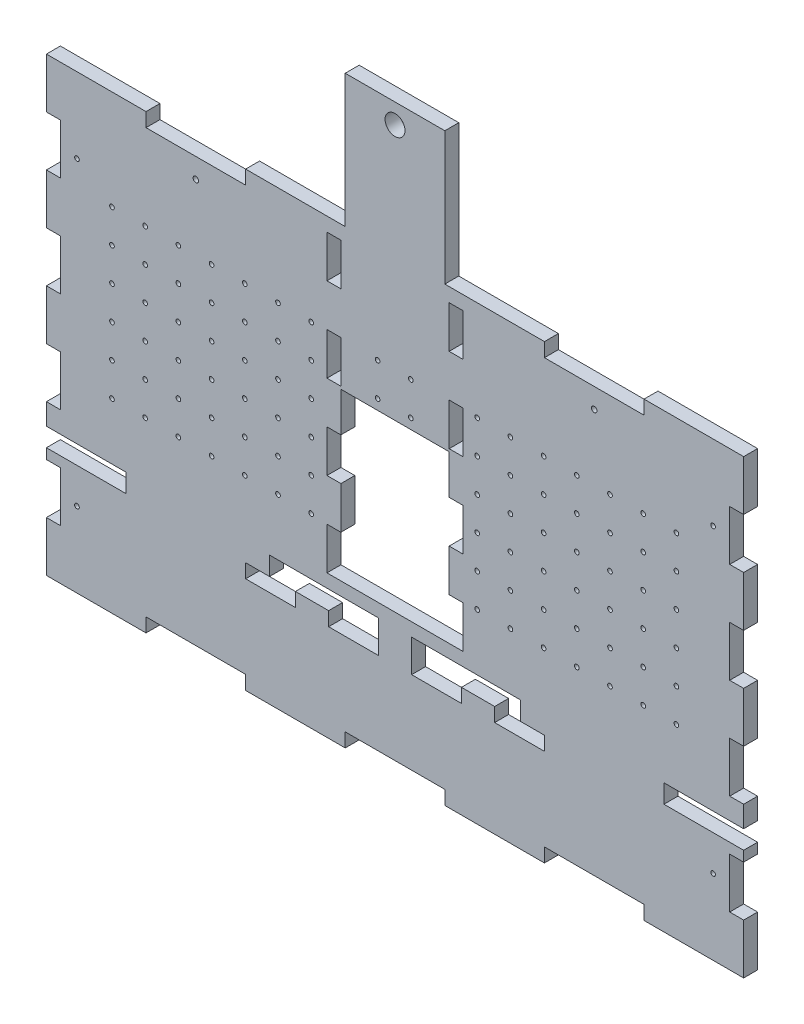
SolidWorks part; units mm, degrees
ref_plane "Front Plane" through (0, 0, 0) normal (0, 0, 1) x (1, 0, 0)
ref_plane "Top Plane" through (0, 0, 0) normal (0, 1, 0) x (1, 0, 0)
ref_plane "Right Plane" through (0, 0, 0) normal (1, 0, 0) x (0, 0, -1)
sketch "Sketch1" plane through (0, 0, 0) normal (0, 0, 1) x (1, 0, 0)
  line L1 (-127.8759, 88.4641) -> (138.8241, 88.4641)
  line L2 (-127.8759, 88.4641) -> (-127.8759, -84.2559)
  line L3 (-127.8759, -84.2559) -> (138.8241, -84.2559)
  line L4 (138.8241, 88.4641) -> (138.8241, -84.2559)
  dimension "D1" = 266.7
  dimension "D2" = 172.72
extrude "Boss-Extrude1" add sketch "Sketch1" along normal blind 5.334
sketch "Sketch2" plane through (0, 0, 5.334) normal (0, 0, 1) x (1, 0, 0)
  line L0 (-127.8759, -84.2559) -> (138.8241, -84.2559) construction
  line L1 (-89.7759, -84.2559) -> (-51.6759, -84.2559)
  line L2 (-89.7759, -84.2559) -> (-89.7759, -78.9219)
  line L3 (-89.7759, -78.9219) -> (-51.6759, -78.9219)
  line L4 (-51.6759, -84.2559) -> (-51.6759, -78.9219)
  line L5 (-89.7759, -78.9219) -> (-127.8759, -78.9219) construction
  line L6 (-13.5759, -84.2559) -> (24.5241, -84.2559)
  line L7 (-13.5759, -84.2559) -> (-13.5759, -78.9219)
  line L8 (-13.5759, -78.9219) -> (24.5241, -78.9219)
  line L9 (24.5241, -84.2559) -> (24.5241, -78.9219)
  line L10 (62.6241, -84.2559) -> (100.7241, -84.2559)
  line L11 (62.6241, -84.2559) -> (62.6241, -78.9219)
  line L12 (62.6241, -78.9219) -> (100.7241, -78.9219)
  line L13 (100.7241, -84.2559) -> (100.7241, -78.9219)
  line L14 (-127.8759, 88.4641) -> (-127.8759, -84.2559) construction
  line L15 (-51.6759, -78.9219) -> (-13.5759, -78.9219) construction
  line L16 (24.5241, -78.9219) -> (62.6241, -78.9219) construction
  line L17 (62.6241, -78.9219) -> (62.364, -79.7896) construction
  line L18 (100.7241, -78.9219) -> (138.8241, -78.9219) construction
  line L19 (138.8241, -84.2559) -> (138.8241, 88.4641) construction
  line L20 (-127.8759, 2.1041) -> (138.8241, 2.1041) construction
  line L21 (100.7241, 88.4641) -> (100.7241, 83.1301)
  line L22 (62.6241, 83.1301) -> (100.7241, 83.1301)
  line L23 (62.6241, 88.4641) -> (62.6241, 83.1301)
  line L24 (24.5241, 88.4641) -> (24.5241, 83.1301)
  line L25 (-13.5759, 83.1301) -> (24.5241, 83.1301)
  line L26 (-13.5759, 88.4641) -> (-13.5759, 83.1301)
  line L27 (-51.6759, 88.4641) -> (-51.6759, 83.1301)
  line L28 (-89.7759, 83.1301) -> (-51.6759, 83.1301)
  line L29 (-89.7759, 88.4641) -> (-89.7759, 83.1301)
  line L30 (62.6241, 88.4641) -> (100.7241, 88.4641)
  line L31 (-13.5759, 88.4641) -> (24.5241, 88.4641)
  line L32 (-89.7759, 88.4641) -> (-51.6759, 88.4641)
  dimension "D1" = 5.334
extrude "Cut-Extrude1" cut sketch "Sketch2" against normal through all
sketch "Sketch5" plane through (0, 0, 5.334) normal (0, 0, 1) x (1, 0, 0)
  line L0 (5.4741, 83.1301) -> (5.4741, -78.9219) construction
  line L1 (-13.5759, 83.1301) -> (24.5241, 83.1301) construction
  line L2 (24.5241, -78.9219) -> (-13.5759, -78.9219) construction
  line L3 (11.8241, -34.8224) -> (11.8241, -41.9344)
  line L4 (-42.5319, -34.8224) -> (-0.8759, -34.8224)
  line L5 (-42.5319, -34.8224) -> (-42.5319, -41.9344)
  line L6 (-42.5319, -41.9344) -> (-0.8759, -41.9344)
  line L7 (-0.8759, -34.8224) -> (-0.8759, -41.9344)
  line L8 (53.4801, -41.9344) -> (11.8241, -41.9344)
  line L9 (53.4801, -34.8224) -> (53.4801, -41.9344)
  line L10 (53.4801, -34.8224) -> (11.8241, -34.8224)
  line L11 (11.8241, -34.8224) -> (-0.8759, -34.8224) construction
  line L12 (-0.8759, -41.9344) -> (11.8241, -41.9344) construction
  line L13 (-139.0519, -34.8224) -> (-97.3959, -34.8224)
  line L14 (-139.0519, -34.8224) -> (-139.0519, -41.9344)
  line L15 (-139.0519, -41.9344) -> (-97.3959, -41.9344)
  line L16 (-97.3959, -34.8224) -> (-97.3959, -41.9344)
  line L18 (108.3441, -34.8224) -> (108.3441, -41.9344)
  line L19 (150.0001, -41.9344) -> (108.3441, -41.9344)
  line L20 (150.0001, -34.8224) -> (150.0001, -41.9344)
  line L21 (150.0001, -34.8224) -> (108.3441, -34.8224)
  dimension "D2" = 41.656
  dimension "D3" = 6.35
  dimension "D1" = 7.112
  dimension "D4" = 2
extrude "Cut-Extrude3" cut sketch "Sketch5" against normal through all
sketch "Sketch9" plane through (0, 0, 5.334) normal (0, 0, 1) x (1, 0, 0)
  line L0 (-127.8759, 88.4641) -> (-127.8759, -34.8224) construction
  line L1 (-127.8759, -65.0647) -> (-122.5419, -65.0647)
  line L2 (-127.8759, -65.0647) -> (-127.8759, -45.8736)
  line L3 (-127.8759, -45.8736) -> (-122.5419, -45.8736)
  line L4 (-122.5419, -65.0647) -> (-122.5419, -45.8736)
  line L5 (-122.5419, 69.273) -> (-122.5419, 88.4641) construction
  line L6 (-127.8759, -26.6825) -> (-122.5419, -26.6825)
  line L7 (-127.8759, -26.6825) -> (-127.8759, -7.4914)
  line L8 (-127.8759, -7.4914) -> (-122.5419, -7.4914)
  line L9 (-122.5419, -26.6825) -> (-122.5419, -7.4914)
  line L10 (-127.8759, 11.6997) -> (-122.5419, 11.6997)
  line L11 (-127.8759, 11.6997) -> (-127.8759, 30.8908)
  line L12 (-127.8759, 30.8908) -> (-122.5419, 30.8908)
  line L13 (-122.5419, 11.6997) -> (-122.5419, 30.8908)
  line L14 (-127.8759, 50.0819) -> (-122.5419, 50.0819)
  line L15 (-127.8759, 50.0819) -> (-127.8759, 69.273)
  line L16 (-127.8759, 69.273) -> (-122.5419, 69.273)
  line L17 (-122.5419, 50.0819) -> (-122.5419, 69.273)
  line L18 (-89.7759, 88.4641) -> (-127.8759, 88.4641) construction
  line L19 (-122.5419, 50.0819) -> (-122.5419, 30.8908) construction
  line L20 (-122.5419, 11.6997) -> (-122.5419, -7.4914) construction
  line L21 (-122.5419, -26.6825) -> (-122.5419, -45.8736) construction
  line L22 (-122.5419, -65.0647) -> (-122.5419, -84.2559) construction
  line L23 (-127.8759, -84.2559) -> (-89.7759, -84.2559) construction
  line L24 (5.4741, 83.1301) -> (5.4741, -78.9219) construction
  line L25 (-13.5759, 83.1301) -> (24.5241, 83.1301) construction
  line L26 (24.5241, -78.9219) -> (-13.5759, -78.9219) construction
  line L27 (133.4901, -65.0647) -> (133.4901, -84.2559) construction
  line L28 (133.4901, -26.6825) -> (133.4901, -45.8736) construction
  line L29 (133.4901, 11.6997) -> (133.4901, -7.4914) construction
  line L30 (133.4901, 50.0819) -> (133.4901, 30.8908) construction
  line L31 (133.4901, 69.273) -> (133.4901, 88.4641) construction
  line L32 (133.4901, 50.0819) -> (133.4901, 69.273)
  line L33 (138.8241, 69.273) -> (133.4901, 69.273)
  line L34 (138.8241, 50.0819) -> (138.8241, 69.273)
  line L35 (138.8241, 50.0819) -> (133.4901, 50.0819)
  line L36 (133.4901, 11.6997) -> (133.4901, 30.8908)
  line L37 (138.8241, 30.8908) -> (133.4901, 30.8908)
  line L38 (138.8241, 11.6997) -> (138.8241, 30.8908)
  line L39 (138.8241, 11.6997) -> (133.4901, 11.6997)
  line L40 (133.4901, -26.6825) -> (133.4901, -7.4914)
  line L41 (138.8241, -7.4914) -> (133.4901, -7.4914)
  line L42 (138.8241, -26.6825) -> (138.8241, -7.4914)
  line L43 (138.8241, -26.6825) -> (133.4901, -26.6825)
  line L44 (133.4901, -65.0647) -> (133.4901, -45.8736)
  line L45 (138.8241, -45.8736) -> (133.4901, -45.8736)
  line L46 (138.8241, -65.0647) -> (138.8241, -45.8736)
  line L47 (138.8241, -65.0647) -> (133.4901, -65.0647)
  dimension "D1" = 5.334
extrude "Cut-Extrude7" cut sketch "Sketch9" against normal through all
sketch "Sketch10" plane through (0, 88.4641, 0) normal (0, 1, 0) x (1, 0, 0)
  line L1 (24.5241, -5.334) -> (62.6241, -5.334)
  line L2 (24.5241, -5.334) -> (24.5241, 0)
  line L3 (24.5241, 0) -> (62.6241, 0)
  line L4 (62.6241, -5.334) -> (62.6241, 0)
extrude "Boss-Extrude2" add sketch "Sketch10" along normal blind 50.8
sketch "Sketch11" plane through (0, 0, 0) normal (0, 0, -1) x (-1, 0, 0)
  line L0 (-24.5241, 83.1301) -> (-24.5241, 139.2641) construction
  line L1 (-24.5241, 88.4641) -> (-31.1281, 88.4641)
  line L2 (-24.5241, 88.4641) -> (-24.5241, 129.1041)
  line L3 (-24.5241, 129.1041) -> (-31.1281, 129.1041)
  line L4 (-31.1281, 88.4641) -> (-31.1281, 129.1041)
  line L5 (13.5759, 88.4641) -> (51.6759, 88.4641) construction
  dimension "D1" = 6.604
  dimension "D3" = 0
extrude "Cut-Extrude8" cut sketch "Sketch11" against normal through all
sketch "Sketch12" plane through (0, 0, 5.334) normal (0, 0, 1) x (1, 0, 0)
  line L0 (62.6241, 139.2641) -> (62.6241, 83.1301) construction
  circle A0 centre (43.5741, 130.4765) radius 3.81
  dimension "D1" = 19.05
extrude "Cut-Extrude9" cut sketch "Sketch12" against normal through all
sketch "Sketch14" plane through (0, 0, 5.334) normal (0, 0, 1) x (1, 0, 0)
  line L0 (-89.7759, 88.4641) -> (-127.8759, 88.4641) construction
  circle A0 centre (-102.7976, 50.3641) radius 0.889
  circle A1 centre (-90.0976, 50.3641) radius 0.889
  circle A2 centre (-77.3976, 50.3641) radius 0.889
  circle A3 centre (-64.6976, 50.3641) radius 0.889
  circle A4 centre (-51.9976, 50.3641) radius 0.889
  circle A5 centre (-39.2976, 50.3641) radius 0.889
  circle A6 centre (-26.5976, 50.3641) radius 0.889
  circle A8 centre (-1.1976, 50.3641) radius 0.889
  circle A9 centre (11.5024, 50.3641) radius 0.889
  circle A11 centre (36.9024, 50.3641) radius 0.889
  circle A12 centre (49.6024, 50.3641) radius 0.889
  circle A13 centre (62.3024, 50.3641) radius 0.889
  circle A14 centre (75.0024, 50.3641) radius 0.889
  circle A15 centre (87.7024, 50.3641) radius 0.889
  circle A16 centre (100.4024, 50.3641) radius 0.889
  circle A17 centre (113.1024, 50.3641) radius 0.889
  circle A18 centre (-102.7976, 37.6641) radius 0.889
  circle A19 centre (-90.0976, 37.6641) radius 0.889
  circle A20 centre (-77.3976, 37.6641) radius 0.889
  circle A21 centre (-64.6976, 37.6641) radius 0.889
  circle A22 centre (-51.9976, 37.6641) radius 0.889
  circle A23 centre (-39.2976, 37.6641) radius 0.889
  circle A24 centre (-26.5976, 37.6641) radius 0.889
  circle A26 centre (-1.1976, 37.6641) radius 0.889
  circle A27 centre (11.5024, 37.6641) radius 0.889
  circle A29 centre (36.9024, 37.6641) radius 0.889
  circle A30 centre (49.6024, 37.6641) radius 0.889
  circle A31 centre (62.3024, 37.6641) radius 0.889
  circle A32 centre (75.0024, 37.6641) radius 0.889
  circle A33 centre (87.7024, 37.6641) radius 0.889
  circle A34 centre (100.4024, 37.6641) radius 0.889
  circle A35 centre (113.1024, 37.6641) radius 0.889
  circle A36 centre (-102.7976, 24.9641) radius 0.889
  circle A37 centre (-90.0976, 24.9641) radius 0.889
  circle A38 centre (-77.3976, 24.9641) radius 0.889
  circle A39 centre (-64.6976, 24.9641) radius 0.889
  circle A40 centre (-51.9976, 24.9641) radius 0.889
  circle A41 centre (-39.2976, 24.9641) radius 0.889
  circle A42 centre (-26.5976, 24.9641) radius 0.889
  circle A44 centre (-1.1976, 24.9641) radius 0.889
  circle A45 centre (11.5024, 24.9641) radius 0.889
  circle A47 centre (36.9024, 24.9641) radius 0.889
  circle A48 centre (49.6024, 24.9641) radius 0.889
  circle A49 centre (62.3024, 24.9641) radius 0.889
  circle A50 centre (75.0024, 24.9641) radius 0.889
  circle A51 centre (87.7024, 24.9641) radius 0.889
  circle A52 centre (100.4024, 24.9641) radius 0.889
  circle A53 centre (113.1024, 24.9641) radius 0.889
  circle A54 centre (-102.7976, 12.2641) radius 0.889
  circle A55 centre (-90.0976, 12.2641) radius 0.889
  circle A56 centre (-77.3976, 12.2641) radius 0.889
  circle A57 centre (-64.6976, 12.2641) radius 0.889
  circle A58 centre (-51.9976, 12.2641) radius 0.889
  circle A59 centre (-39.2976, 12.2641) radius 0.889
  circle A60 centre (-26.5976, 12.2641) radius 0.889
  circle A65 centre (36.9024, 12.2641) radius 0.889
  circle A66 centre (49.6024, 12.2641) radius 0.889
  circle A67 centre (62.3024, 12.2641) radius 0.889
  circle A68 centre (75.0024, 12.2641) radius 0.889
  circle A69 centre (87.7024, 12.2641) radius 0.889
  circle A70 centre (100.4024, 12.2641) radius 0.889
  circle A71 centre (113.1024, 12.2641) radius 0.889
  circle A72 centre (-102.7976, -0.4359) radius 0.889
  circle A73 centre (-90.0976, -0.4359) radius 0.889
  circle A74 centre (-77.3976, -0.4359) radius 0.889
  circle A75 centre (-64.6976, -0.4359) radius 0.889
  circle A76 centre (-51.9976, -0.4359) radius 0.889
  circle A77 centre (-39.2976, -0.4359) radius 0.889
  circle A78 centre (-26.5976, -0.4359) radius 0.889
  circle A79 centre (-13.8976, -0.4359) radius 0.889
  circle A80 centre (-1.1976, -0.4359) radius 0.889
  circle A81 centre (11.5024, -0.4359) radius 0.889
  circle A82 centre (24.2024, -0.4359) radius 0.889
  circle A83 centre (36.9024, -0.4359) radius 0.889
  circle A84 centre (49.6024, -0.4359) radius 0.889
  circle A85 centre (62.3024, -0.4359) radius 0.889
  circle A86 centre (75.0024, -0.4359) radius 0.889
  circle A87 centre (87.7024, -0.4359) radius 0.889
  circle A88 centre (100.4024, -0.4359) radius 0.889
  circle A89 centre (113.1024, -0.4359) radius 0.889
  circle A90 centre (-102.7976, -13.1359) radius 0.889
  circle A91 centre (-90.0976, -13.1359) radius 0.889
  circle A92 centre (-77.3976, -13.1359) radius 0.889
  circle A93 centre (-64.6976, -13.1359) radius 0.889
  circle A94 centre (-51.9976, -13.1359) radius 0.889
  circle A95 centre (-39.2976, -13.1359) radius 0.889
  circle A96 centre (-26.5976, -13.1359) radius 0.889
  circle A97 centre (-13.8976, -13.1359) radius 0.889
  circle A98 centre (-1.1976, -13.1359) radius 0.889
  circle A99 centre (11.5024, -13.1359) radius 0.889
  circle A100 centre (24.2024, -13.1359) radius 0.889
  circle A101 centre (36.9024, -13.1359) radius 0.889
  circle A102 centre (49.6024, -13.1359) radius 0.889
  circle A103 centre (62.3024, -13.1359) radius 0.889
  circle A104 centre (75.0024, -13.1359) radius 0.889
  circle A105 centre (87.7024, -13.1359) radius 0.889
  circle A106 centre (100.4024, -13.1359) radius 0.889
  circle A107 centre (113.1024, -13.1359) radius 0.889
  circle A108 centre (-1.1976, 12.2641) radius 0.889 [skipped]
  circle A110 centre (11.5024, 12.2641) radius 0.889 [skipped]
  circle A116 centre (24.2024, 50.3641) radius 0.889 [skipped]
  circle A117 centre (-13.8976, 50.3641) radius 0.889 [skipped]
  dimension "D1" = 18
  dimension "D2" = 38.1
  dimension "D4" = 1.778
  dimension "D3" = 6
extrude "Cut-Extrude11" cut sketch "Sketch14" against normal through all
sketch "Sketch15" plane through (0, 0, 5.334) normal (0, 0, 1) x (1, 0, 0)
  line L1 (31.1281, 129.1041) -> (24.5241, 129.1041)
  line L2 (31.1281, 129.1041) -> (31.1281, 139.2641)
  line L3 (31.1281, 139.2641) -> (24.5241, 139.2641)
  line L4 (24.5241, 129.1041) -> (24.5241, 139.2641)
extrude "Cut-Extrude12" cut sketch "Sketch15" against normal through all
sketch "Sketch16" plane through (0, 0, 5.334) normal (0, 0, 1) x (1, 0, 0)
  line L0 (5.4741, 83.1301) -> (5.4741, -78.9219) construction
  line L1 (-15.2269, 33.7576) -> (26.1751, 33.7576)
  line L2 (-15.2269, 33.7576) -> (-15.2269, -29.7424)
  line L3 (-15.2269, -29.7424) -> (26.1751, -29.7424)
  line L4 (26.1751, 33.7576) -> (26.1751, -29.7424)
  line L5 (-13.5759, 83.1301) -> (24.5241, 83.1301) construction
  line L6 (24.5241, -78.9219) -> (-13.5759, -78.9219) construction
  line L8 (-0.8759, -34.8224) -> (-42.5319, -34.8224) construction
  dimension "D1" = 63.5
  dimension "D2" = 41.402
  dimension "D3" = 20.701
  dimension "D4" = 5.08
extrude "Cut-Extrude13" cut sketch "Sketch16" against normal through all
sketch "Sketch17" plane through (0, 0, 5.334) normal (0, 0, 1) x (1, 0, 0)
  line L0 (-15.2269, 33.7576) -> (-15.2269, -29.7424) construction
  line L1 (-15.2269, -29.7424) -> (-20.5609, -29.7424)
  line L2 (-15.2269, -29.7424) -> (-15.2269, -13.6178)
  line L3 (-15.2269, -13.6178) -> (-20.5609, -13.6178)
  line L4 (-20.5609, -29.7424) -> (-20.5609, -13.6178)
  line L5 (-15.2269, 2.5069) -> (-20.5609, 2.5069)
  line L6 (-15.2269, 2.5069) -> (-15.2269, 18.6315)
  line L7 (-15.2269, 18.6315) -> (-20.5609, 18.6315)
  line L8 (-20.5609, 2.5069) -> (-20.5609, 18.6315)
  line L9 (-20.5609, -13.6178) -> (-20.5609, 2.5069) construction
  line L10 (-20.5609, 50.8808) -> (-15.2269, 50.8808)
  line L11 (-20.5609, 50.8808) -> (-20.5609, 34.7562)
  line L12 (-20.5609, 34.7562) -> (-15.2269, 34.7562)
  line L13 (-15.2269, 50.8808) -> (-15.2269, 34.7562)
  line L14 (-20.5609, 67.0055) -> (-15.2269, 67.0055)
  line L15 (-20.5609, 67.0055) -> (-20.5609, 83.1301)
  line L16 (-20.5609, 83.1301) -> (-15.2269, 83.1301)
  line L17 (-15.2269, 67.0055) -> (-15.2269, 83.1301)
  line L18 (-20.5609, 18.6315) -> (-20.5609, 34.7562) construction
  line L19 (-20.5609, 67.0055) -> (-20.5609, 50.8808) construction
  line L20 (5.4741, 83.1301) -> (5.4741, -78.9219) construction
  line L21 (-13.5759, 83.1301) -> (24.5241, 83.1301) construction
  line L22 (24.5241, -78.9219) -> (-13.5759, -78.9219) construction
  line L23 (31.5091, 67.0055) -> (31.5091, 50.8808) construction
  line L24 (31.5091, 18.6315) -> (31.5091, 34.7562) construction
  line L25 (31.5091, -13.6178) -> (31.5091, 2.5069) construction
  line L26 (26.1751, 67.0055) -> (26.1751, 83.1301)
  line L27 (31.5091, 83.1301) -> (26.1751, 83.1301)
  line L28 (31.5091, 67.0055) -> (31.5091, 83.1301)
  line L29 (31.5091, 67.0055) -> (26.1751, 67.0055)
  line L30 (26.1751, 50.8808) -> (26.1751, 34.7562)
  line L31 (31.5091, 34.7562) -> (26.1751, 34.7562)
  line L32 (31.5091, 50.8808) -> (31.5091, 34.7562)
  line L33 (31.5091, 50.8808) -> (26.1751, 50.8808)
  line L34 (31.5091, 2.5069) -> (31.5091, 18.6315)
  line L35 (26.1751, 18.6315) -> (31.5091, 18.6315)
  line L36 (26.1751, 2.5069) -> (26.1751, 18.6315)
  line L37 (26.1751, 2.5069) -> (31.5091, 2.5069)
  line L38 (31.5091, -29.7424) -> (31.5091, -13.6178)
  line L39 (26.1751, -13.6178) -> (31.5091, -13.6178)
  line L40 (26.1751, -29.7424) -> (26.1751, -13.6178)
  line L41 (26.1751, -29.7424) -> (31.5091, -29.7424)
  dimension "D1" = 0
  dimension "D2" = 5.334
  dimension "D3" = 5.334
  dimension "D4" = 5.334
extrude "Cut-Extrude14" cut sketch "Sketch17" against normal through all
sketch "Sketch18" plane through (0, 0, 5.334) normal (0, 0, 1) x (1, 0, 0)
  line L0 (24.5241, 83.1301) -> (24.5241, 148.9274) construction
  line L1 (31.1281, 139.2641) -> (62.6241, 139.2641) construction
  line L2 (-13.5759, 83.1301) -> (24.5241, 83.1301)
  line L3 (-13.5759, 83.1301) -> (-13.5759, 139.2641)
  line L4 (-13.5759, 139.2641) -> (24.5241, 139.2641)
  line L5 (24.5241, 83.1301) -> (24.5241, 139.2641)
  dimension "D1" = 0
extrude "Boss-Extrude3" add sketch "Sketch18" against normal blind 5.334
sketch "Sketch19" plane through (0, 0, 5.334) normal (0, 0, 1) x (1, 0, 0)
  line L1 (31.1281, 88.4641) -> (65.8849, 88.4641)
  line L2 (31.1281, 88.4641) -> (31.1281, 143.4078)
  line L3 (31.1281, 143.4078) -> (65.8849, 143.4078)
  line L4 (65.8849, 88.4641) -> (65.8849, 143.4078)
extrude "Cut-Extrude15" cut sketch "Sketch19" against normal through all
sketch "Sketch20" plane through (0, 0, 5.334) normal (0, 0, 1) x (1, 0, 0)
  line L0 (5.4741, 139.2641) -> (5.4741, 29.9476) construction
  line L1 (24.5241, 139.2641) -> (-13.5759, 139.2641) construction
  circle A0 centre (5.4741, 131.6441) radius 3.81
  dimension "D1" = 7.62
  dimension "D3" = 7.62
  dimension "D2" = 0
extrude "Cut-Extrude16" cut sketch "Sketch20" against normal through all contours A0
sketch "Sketch21" plane through (0, 0, 5.334) normal (0, 0, 1) x (1, 0, 0)
  line L0 (133.4901, 59.6775) -> (-122.5419, 59.6775) construction
  line L1 (133.4901, 69.273) -> (133.4901, 50.0819) construction
  line L2 (-122.5419, 50.0819) -> (-122.5419, 69.273) construction
  line L3 (-122.5419, -55.4692) -> (133.4901, -55.4692) construction
  line L4 (-122.5419, -65.0647) -> (-122.5419, -45.8736) construction
  line L5 (133.4901, -45.8736) -> (133.4901, -65.0647) construction
  line L6 (138.8241, 2.1041) -> (-127.8759, 2.1041) construction
  line L7 (138.8241, -7.4914) -> (138.8241, 11.6997) construction
  line L8 (-127.8759, 11.6997) -> (-127.8759, -7.4914) construction
  line L9 (5.4741, 139.2641) -> (5.4741, -78.9219) construction
  line L10 (24.5241, 139.2641) -> (-13.5759, 139.2641) construction
  line L11 (24.5241, -78.9219) -> (-13.5759, -78.9219) construction
  circle A0 centre (127.1401, 59.6775) radius 0.889
  circle A1 centre (-116.1919, 59.6775) radius 0.889
  circle A2 centre (-116.1919, -55.4692) radius 0.889
  circle A3 centre (127.1401, -55.4692) radius 0.889
  dimension "D1" = 1.778
  dimension "D2" = 0
  dimension "D3" = 6.35
extrude "Cut-Extrude17" cut sketch "Sketch21" against normal through all
sketch "Sketch22" plane through (0, 0, 0) normal (0, 0, -1) x (-1, 0, 0)
  line L0 (-11.8241, -41.9344) -> (-53.4801, -41.9344) construction
  line L1 (-30.8741, -41.9344) -> (-11.8241, -41.9344)
  line L2 (-30.8741, -41.9344) -> (-30.8741, -47.2684)
  line L3 (-30.8741, -47.2684) -> (-11.8241, -47.2684)
  line L4 (-11.8241, -41.9344) -> (-11.8241, -47.2684)
  line L5 (-11.8241, -34.8224) -> (-11.8241, -41.9344) construction
  line L6 (-62.6241, -47.2684) -> (-43.5741, -47.2684)
  line L7 (-43.5741, -41.9344) -> (-43.5741, -47.2684)
  line L8 (-62.6241, -41.9344) -> (-43.5741, -41.9344)
  line L9 (-62.6241, -41.9344) -> (-62.6241, -47.2684)
  line L10 (-5.4741, -78.9219) -> (-5.4741, 95.0308) construction
  line L11 (-24.5241, -78.9219) -> (13.5759, -78.9219) construction
  line L12 (51.6759, -41.9344) -> (51.6759, -47.2684)
  line L13 (51.6759, -41.9344) -> (32.6259, -41.9344)
  line L14 (32.6259, -41.9344) -> (32.6259, -47.2684)
  line L15 (51.6759, -47.2684) -> (32.6259, -47.2684)
  line L16 (0.8759, -41.9344) -> (0.8759, -47.2684)
  line L17 (19.9259, -47.2684) -> (0.8759, -47.2684)
  line L18 (19.9259, -41.9344) -> (19.9259, -47.2684)
  line L19 (19.9259, -41.9344) -> (0.8759, -41.9344)
  dimension "D4" = 5.334
  dimension "D1" = 19.05
  dimension "D2" = 0
  dimension "D3" = 2
extrude "Cut-Extrude18" cut sketch "Sketch22" against normal through all
sketch "Sketch23" plane through (0, 0, 0) normal (0, 0, -1) x (-1, 0, 0)
  line L0 (-81.6741, 83.1301) -> (-81.6741, 61.0847) construction
  line L1 (-62.6241, 83.1301) -> (-100.7241, 83.1301) construction
  line L2 (-5.4741, 139.2641) -> (-5.4741, 93.6801) construction
  line L3 (-24.5241, 139.2641) -> (13.5759, 139.2641) construction
  circle A0 centre (-81.6741, 75.5101) radius 1.0477
  circle A1 centre (70.7259, 75.5101) radius 1.0477
  dimension "D1" = 2.0955
  dimension "D2" = 0
  dimension "D3" = 7.62
extrude "Cut-Extrude19" cut sketch "Sketch23" against normal through all
equation "\"MDF\"= .21in"
equation "\"Foamcore\"= .13in"
equation "\"Gmaterial\"= \"MDF\""
equation "\"D1@Boss-Extrude1\"=\"MDF\""
equation "\"D1@Sketch2\"=\"MDF\""
equation "\"D1@Sketch5\"=\"MDF\"+0.07"
equation "\"D1@Sketch9\"=\"MDF\""
equation "\"D1@Sketch11\"=\"MDF\"+.05"
equation "\"D2@Sketch17\"=\"MDF\""
equation "\"D3@Sketch17\"=\"MDF\""
equation "\"D4@Sketch17\"=\"MDF\""
equation "\"D1@Boss-Extrude3\"=\"MDF\""
equation "\"D4@Sketch22\"=\"MDF\""
